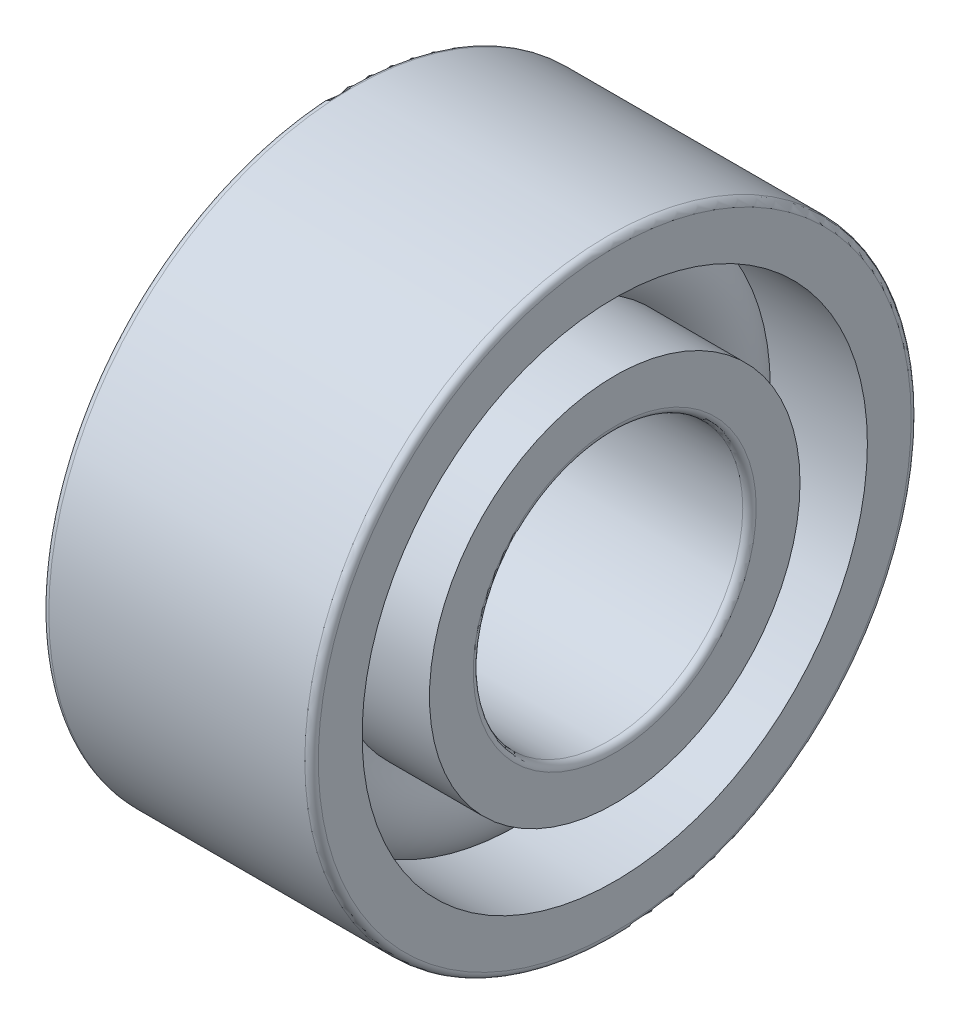
SolidWorks part; units mm, degrees
ref_plane "Plane1" through (0, 0, 0) normal (0, 0, 1) x (1, 0, 0)
ref_plane "Plane2" through (0, 0, 0) normal (0, 1, 0) x (1, 0, 0)
ref_plane "Plane3" through (0, 0, 0) normal (1, 0, 0) x (0, 0, -1)
sketch "Clipboard" plane through (0, 0, 0) normal (0, 0, 1) x (1, 0, 0)
  line L0 (-10, 0) -> (10, 0) construction
  line L1 (0, 0) -> (22.3471, -0.7804)
  line L2 (0, 0) -> (3.248, 0.1134)
  line L3 (0, 0) -> (22.3471, -0.7804)
  line L4 (0, 0) -> (-22.3573, -0.3902)
  dimension "BallCLRad" = 3.25
sketch "CagSpiSke" plane through (0, 0, 0) normal (0, 0, 1) x (1, 0, 0)
  line L0 (0.075, 3.125) -> (0.075, 3.375)
  line L1 (0.075, 3.375) -> (-0.075, 3.375)
  line L2 (-0.075, 3.375) -> (-0.075, 3.125)
  line L3 (-0.075, 3.125) -> (0.075, 3.125)
  line L4 (-20.6375, 0) -> (20.6375, 0) construction
  line L5 (0, 0) -> (0, 23.7692) construction
  dimension "OD" = 6.75
  dimension "ID" = 6.25
revolve "CageSpine" add sketch "CagSpiSke" angle 0.001 about L4 reverse direction yes
ref_axis "Axis1" through (-50, 0, 0) along (1, 0, 0)
sketch "CagBalSke" plane through (0, 0, 0) normal (0, 0, 1) x (1, 0, 0)
  line L0 (-0.825, 3.25) -> (0.825, 3.25)
  line L1 (-1.905, 3.25) -> (1.905, 3.25) construction
  line L2 (-10, 0) -> (10, 0) construction
  line L3 (0, 0) -> (0, 24) construction
  arc A0 (0.825, 3.25) -> (-0.825, 3.25) centre (0, 3.25) cw
  dimension "BallCLRad" = 3.25
revolve "CageBall" [suppressed] add sketch "CagBalSke" angle 360 about L1 reverse direction yes
pattern_circular "CageBalls" [suppressed] count 2 every 180 about axis through (-50, 0, 0) along (1, 0, 0)
sketch "CagTrmODSke" plane through (0, 0, 0) normal (0, 0, 1) x (1, 0, 0)
  line L0 (0.826, 3.375) -> (0.826, 4.076)
  line L1 (0.826, 4.076) -> (-0.826, 4.076)
  line L2 (-0.826, 4.076) -> (-0.826, 3.375)
  line L3 (-0.826, 3.375) -> (0.826, 3.375)
  line L4 (-20.6375, 0) -> (20.6375, 0) construction
  line L5 (0, 0) -> (0, 25) construction
  dimension "Width" = 1.652
  dimension "ID" = 6.75
  dimension "OD" = 8.152
revolve "CageTrimOD" [suppressed] cut sketch "CagTrmODSke" angle 360 about L4 reverse direction yes
sketch "CagTrmIDSke" plane through (0, 0, 0) normal (0, 0, 1) x (1, 0, 0)
  line L0 (0.826, 2.426) -> (0.826, 3.125)
  line L1 (0.826, 3.125) -> (-0.826, 3.125)
  line L2 (-0.826, 3.125) -> (-0.826, 2.426)
  line L3 (-0.826, 2.426) -> (0.826, 2.426)
  line L4 (-20.6375, 0) -> (20.6375, 0) construction
  line L5 (0, 0) -> (0, 25) construction
  dimension "Width" = 1.652
  dimension "ID" = 4.852
  dimension "OD" = 6.25
revolve "CageTrimID" [suppressed] cut sketch "CagTrmIDSke" angle 360 about L4 reverse direction yes
sketch "BalSimSke" plane through (0, 0, 0) normal (0, 0, 1) x (1, 0, 0)
  line L0 (-10, 0) -> (10, 0) construction
  line L1 (-10, 3.25) -> (10, 3.25) construction
  line L2 (0, 0) -> (0, 23) construction
  circle A0 centre (0, 3.25) radius 0.75
  dimension "BallCLRad" = 3.25
  dimension "Ball_diameter" = 1.5
revolve "BallsSimplified" add sketch "BalSimSke" angle 360 about L0
sketch "BalDetSke" plane through (0, 0, 0) normal (0, 0, 1) x (1, 0, 0)
  line L0 (-0.75, 3.25) -> (0.75, 3.25)
  line L1 (-1.905, 3.25) -> (1.905, 3.25) construction
  line L2 (0, 0) -> (0, 25) construction
  arc A0 (0.75, 3.25) -> (-0.75, 3.25) centre (0, 3.25) cw
  dimension "BallCLRad" = 3.25
  dimension "Ball_diameter" = 1.5
revolve "BallDetailed" [suppressed] add sketch "BalDetSke" angle 360 about L1 reverse direction yes
sketch "InnRacSke" plane through (0, 0, 0) normal (0, 0, 1) x (1, 0, 0)
  line L0 (-0.525, 2.75) -> (-2, 2.75)
  line L1 (-2, 2.75) -> (-2, 2.1)
  line L2 (-1.9, 2) -> (1.9, 2)
  line L3 (2, 2.1) -> (2, 2.75)
  line L4 (2, 2.75) -> (0.525, 2.75)
  line L5 (-20.6375, 0) -> (20.6375, 0) construction
  line L6 (0, 0) -> (0, 30) construction
  arc A0 (-2, 2.1) -> (-1.9, 2) centre (-1.9, 2.1) ccw
  arc A1 (1.9, 2) -> (2, 2.1) centre (1.9, 2.1) ccw
  arc A2 (0.525, 2.75) -> (-0.525, 2.75) centre (0, 3.25) cw
  dimension "BallCLRad" = 3.25
  dimension "Fillet_radius" = 0.1
  dimension "Ball_diameter" = 1.45
  dimension "ID" = 4
  dimension "OD" = 5.5
  dimension "Width" = 4
revolve "InnerRace" add sketch "InnRacSke" angle 360 about L5 reverse direction yes
sketch "OutRacSke" plane through (0, 0, 0) normal (0, 0, 1) x (1, 0, 0)
  line L0 (-0.525, 3.75) -> (-2, 3.75)
  line L1 (-2, 3.75) -> (-2, 4.4)
  line L2 (-1.9, 4.5) -> (1.9, 4.5)
  line L3 (2, 4.4) -> (2, 3.75)
  line L4 (2, 3.75) -> (0.525, 3.75)
  line L5 (-20.6375, 0) -> (20.6375, 0) construction
  line L6 (0, 0) -> (0, 30) construction
  arc A0 (-2, 4.4) -> (-1.9, 4.5) centre (-1.9, 4.4) cw
  arc A1 (1.9, 4.5) -> (2, 4.4) centre (1.9, 4.4) cw
  arc A2 (0.525, 3.75) -> (-0.525, 3.75) centre (0, 3.25) ccw
  dimension "BallCLRad" = 3.25
  dimension "Fillet_radius" = 0.1
  dimension "Ball_diameter" = 1.45
  dimension "Width" = 4
revolve "OuterRace" add sketch "OutRacSke" angle 360 about L5 reverse direction yes
pattern_circular "BallsDetailed" [suppressed] count 2 every 180 about axis through (-50, 0, 0) along (1, 0, 0)
equation "\"BallCLRad@Clipboard\" = ( \"OD@OutRacSke\" + \"ID@InnRacSke\" ) / 4"
equation "\"BallCLRad@BalSimSke\" = \"BallCLRad@Clipboard\""
equation "\"BallCLRad@BalDetSke\" = \"BallCLRad@Clipboard\""
equation "\"BallCLRad@InnRacSke\" = \"BallCLRad@Clipboard\""
equation "\"BallCLRad@OutRacSke\" = \"BallCLRad@Clipboard\""
equation "\"Ball_diameter@InnRacSke\" = \"Ball_diameter@BalDetSke\" - 0.05"
equation "\"Ball_diameter@OutRacSke\" = \"Ball_diameter@BalDetSke\" - 0.05"
equation "\"Ball_diameter@BalSimSke\" = \"Ball_diameter@BalDetSke\""
equation "\"Width@OutRacSke\" = \"Width@InnRacSke\""
equation "\"Fillet_radius@OutRacSke\" = \"Fillet_radius@InnRacSke\""
equation "\"Max_count@Clipboard\" = int( 3.14159265 / atn(( \"Ball_diameter@BalDetSke\" / 2) / sqr( \"BallCLRad@Clipboard\"  *  \"BallCLRad@Clipboard\" - ( \"Ball_diameter@BalDetSke\" / 2) *  ( \"Ball_diameter@BalDetSke\" / 2))))"
equation "\"Max_count@Clipboard\" = ((sgn( \"Max_count@Clipboard\" - \"Count@Clipboard\" )-1)*( \"Max_count@Clipboard\" - \"Count@Clipboard\" ))/-2+ \"Count@Clipboard\""
equation "\"Count@BallsDetailed\" = int( \"Show_count@Clipboard\" ) "
equation "\"Count@BallsDetailed\" = ((sgn( \"Count@BallsDetailed\" - \"Max_count@Clipboard\" )-1)*( \"Count@BallsDetailed\" - \"Max_count@Clipboard\" ))/-2+ \"Max_count@Clipboard\""
equation "\"Count@BallsDetailed\" = ((sgn( \"Count@BallsDetailed\" - \"Min_count@Clipboard\" )+1)*( \"Count@BallsDetailed\" - \"Min_count@Clipboard\"))/2 +\"Min_count@Clipboard\""
equation "\"Angle@BallsDetailed\" = 360.0 / \"Max_count@Clipboard\""
equation "\"BallCLRad@CagBalSke\" = \"BallCLRad@Clipboard\""
equation "\"Count@CageBalls\" = \"Count@BallsDetailed\""
equation "\"Angle@CageBalls\" = \"Angle@BallsDetailed\""
equation "\"Angle@CageSpine\" =  \"Angle@CageBalls\" * ( \"Count@CageBalls\" -1 + int( \"Count@CageBalls\" / \"Max_count@Clipboard\" ) )  + 0.001 -  int( \"Count@CageBalls\" / \"Max_count@Clipboard\" ) * 0.001"
equation "\"Angle@CageSpine\" =  \"Angle@CageSpine\" * int( \"Min_count@Clipboard\" / 2) + int(1 / \"Min_count@Clipboard\")  * 0.001"
equation "\"CageWallOD@CagBalSke\" =  \"Ball_diameter@BalDetSke\" * 1.1"
equation "\"Thickness@CagSpiSke\" =  \"Ball_diameter@BalDetSke\" * 0.1"
equation "\"OD@CagTrmODSke\" = \"BallCLRad@Clipboard\" * 2 + \"CageWallOD@CagBalSke\" + 0.002"
equation "\"ID@CagTrmODSke\" = \"BallCLRad@Clipboard\" * 2 + \"Ball_diameter@BalDetSke\" / 6"
equation "\"OD@CagTrmIDSke\" = \"BallCLRad@Clipboard\" * 2 - \"Ball_diameter@BalDetSke\" / 6"
equation "\"ID@CagTrmIDSke\" = \"BallCLRad@Clipboard\" * 2 - \"CageWallOD@CagBalSke\" + 0.002"
equation "\"OD@CagSpiSke\" = \"ID@CagTrmODSke\""
equation "\"ID@CagSpiSke\" = \"OD@CagTrmIDSke\""
equation "\"Width@CagTrmODSke\" = \"CageWallOD@CagBalSke\" + 0.002"
equation "\"Width@CagTrmIDSke\" = \"CageWallOD@CagBalSke\" + 0.002"
